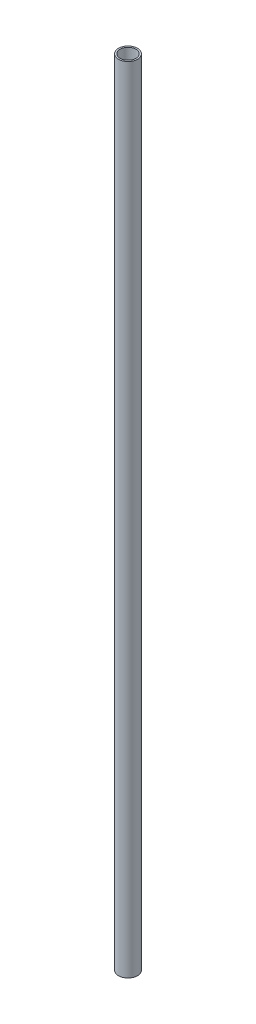
SolidWorks part; units mm, degrees
material "Hexcel AS4C (3000 Filaments)"
ref_plane "Front Plane" through (0, 0, 0) normal (0, 0, 1) x (1, 0, 0)
ref_plane "Top Plane" through (0, 0, 0) normal (0, 1, 0) x (1, 0, 0)
ref_plane "Right Plane" through (0, 0, 0) normal (1, 0, 0) x (0, 0, -1)
sketch "Sketch1" plane through (0, 0, 0) normal (0, 1, 0) x (1, 0, 0)
  circle A0 centre (0, 0) radius 6
  circle A1 centre (0, 0) radius 5
  dimension "D1" = 12
  dimension "D2" = 10
extrude "Boss-Extrude1" add sketch "Sketch1" along normal blind 250 and the other way blind 250
ref_plane "Plane1" through (0, 185, 0) normal (0, 1, 0) x (1, 0, 0)
sketch "Sketch2" plane through (0, 185, 0) normal (0, 1, 0) x (1, 0, 0)
  point P0 (0, 0)
ref_plane "Plane2" through (0, -185, 0) normal (0, -1, 0) x (-1, 0, 0)
sketch "Sketch3" plane through (0, -185, 0) normal (0, -1, 0) x (-1, 0, 0)
  point P0 (0, 0)
